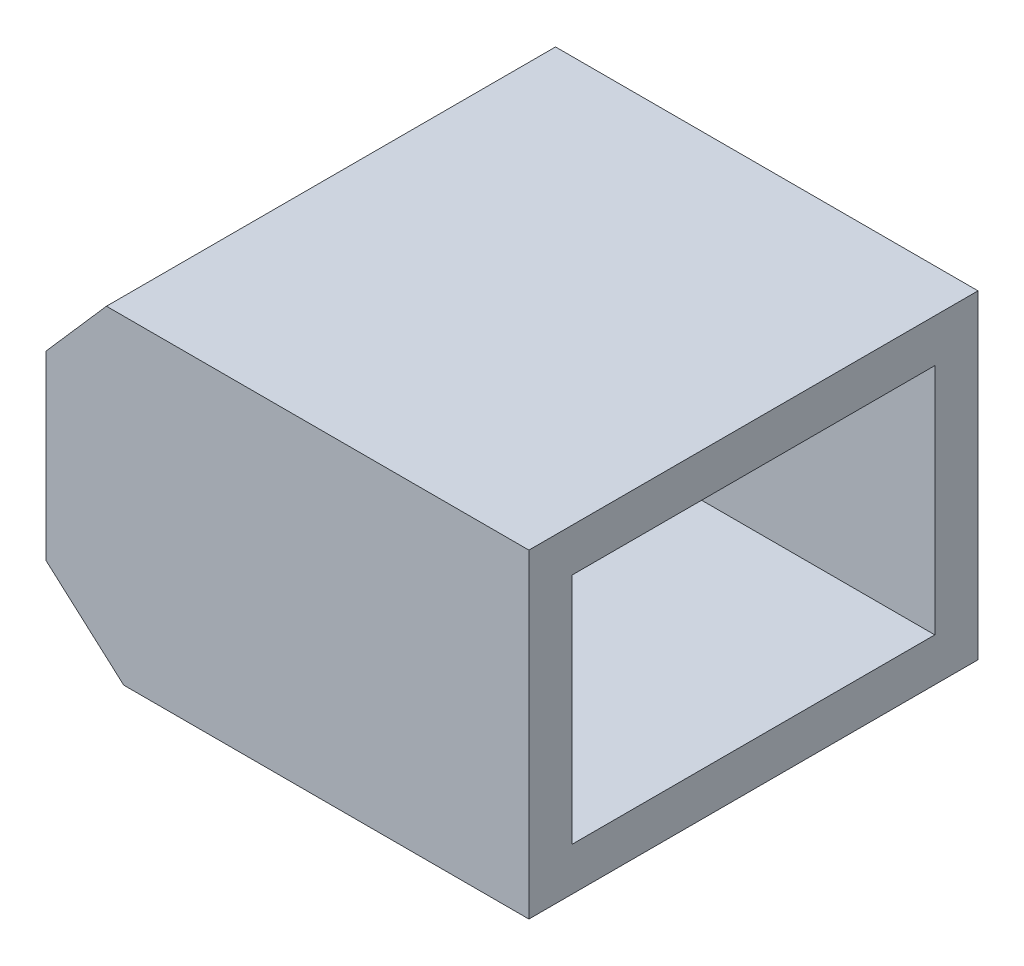
SolidWorks part; units mm, degrees
ref_plane "前视基准面" through (0, 0, 0) normal (0, 0, 1) x (1, 0, 0)
ref_plane "上视基准面" through (0, 0, 0) normal (0, 1, 0) x (1, 0, 0)
ref_plane "右视基准面" through (0, 0, 0) normal (1, 0, 0) x (0, 0, -1)
other "Configuration Table"
sketch "草图1" plane through (0, 0, 0) normal (0, 0, 1) x (1, 0, 0)
  line L0 (0.9152, 0) -> (-48, 0)
  line L1 (-48, 0) -> (-55, -8)
  line L2 (-55, -8) -> (-55, -29)
  line L3 (-55, -29) -> (-46, -37)
  line L4 (-46, -37) -> (0.9152, -37)
  line L5 (0.9152, -37) -> (0.9152, 0)
  dimension "x0" = 0.9152
  dimension "x1" = 48
  dimension "x2" = 55
  dimension "x4" = 46
  dimension "y2" = 8
  dimension "y3" = 29
  dimension "y4" = 37
extrude "Closing_lip_profile" add sketch "草图1" along normal blind 52
shell "抽壳1" thickness 5 removed face at (0.9152, -18.5, 26)
